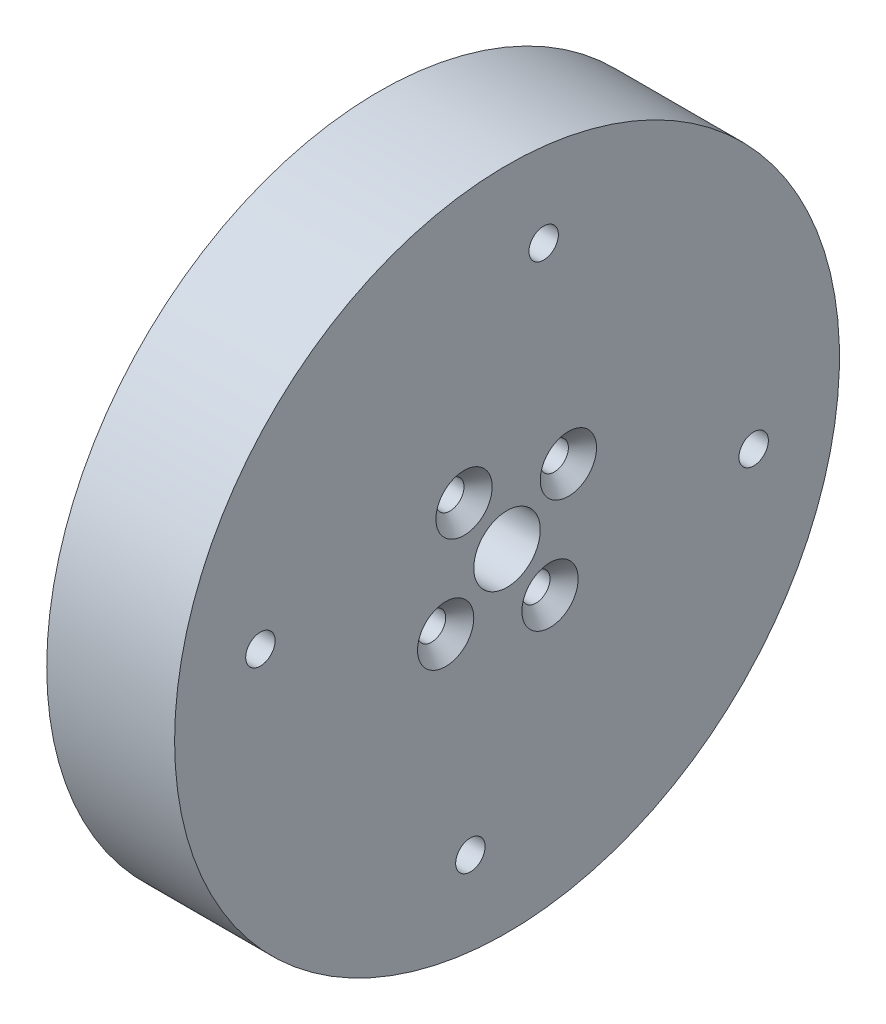
SolidWorks part; units mm, degrees
ref_plane "Спереди" through (0, 0, 0) normal (0, 0, 1) x (1, 0, 0)
ref_plane "Сверху" through (0, 0, 0) normal (0, 1, 0) x (1, 0, 0)
ref_plane "Справа" through (0, 0, 0) normal (1, 0, 0) x (0, 0, -1)
sketch "Эскиз1" plane through (0, 0, 0) normal (0, 0, 1) x (1, 0, 0)
  line L0 (0, 0) -> (100.9242, 0) construction
  line L6 (0, 13) -> (0, 26)
  line L7 (0, 26) -> (10, 26)
  line L11 (5, 13) -> (0, 13)
  line L13 (5, 13) -> (5, 2.6)
  line L14 (5, 2.6) -> (10, 2.6)
  line L15 (10, 2.6) -> (10, 26)
  dimension "D1" = 26
  dimension "D2" = 52
  dimension "D3" = 10
  dimension "D4" = 5
  dimension "D5" = 5.2
revolve "Повернуть1" add sketch "Эскиз1" angle 360 about L0
hole_wizard "Зенковка для  винта с плоской головкой M22" positions "Эскиз4" profile "Эскиз5" countersink size "M2" standard "Ansi Metric" end condition through all
sketch "Эскиз4" plane through (10, 0, 0) normal (1, 0, 0) x (0, 0, -1)
  point P0 (-3.3627, 4.8)
  dimension "D1" = 4.8
sketch "Эскиз5" plane through (10, 4.8, 3.3627) normal (0, 1, 0) x (0, 0, -1)
  line L0 (0, 0) -> (0, 10)
  line L1 (0, 10) -> (1.1, 10)
  line L2 (1.1, 10) -> (1.1, 1.1)
  line L3 (1.1, 1.1) -> (2.2, 0)
  line L5 (2.2, 0) -> (0, 0)
  line L6 (-1.1, 1.1) -> (-2.2, 0) construction
  line L11 (0, -6.35) -> (0, 107.95) construction
  dimension "Диаметр сквозного отверстия" = 2.2
  dimension "Глубина сквозного отверстия" = 10
  dimension "Диаметр передней зенковки" = 4.4
  dimension "Угол передней зенковки" = 90
ref_axis "Ось1" through (10, 0, 0) along (-1, 0, 0)
ref_axis "Ось2" through (10, 0, 0) along (-1, 0, 0)
pattern_circular "Круговой массив2" count 4 over 360 about axis through (10, 0, 0) along (-1, 0, 0) of "Зенковка для  винта с плоской головкой M22"
hole_wizard "Сверло под метчик  спиральное M2.21" positions "Эскиз6" profile "Эскиз7" hole size "M2.2x0.45" standard "Ansi Metric"
sketch "Эскиз6" plane through (10, 0, 0) normal (1, 0, 0) x (0, 0, -1)
  point P0 (19.2882, -2.8664)
  dimension "D1" = 19.5
sketch "Эскиз7" plane through (10, -2.8664, -19.2882) normal (0, 1, 0) x (0, 0, -1)
  line L0 (0, 0) -> (0, 3.691)
  line L1 (0, 3.691) -> (1.15, 3)
  line L2 (1.15, 3) -> (1.15, 0)
  line L5 (1.15, 0) -> (0, 0)
  line L10 (0, 3.691) -> (-1.15, 3) construction
  line L11 (0, -6.35) -> (0, 107.95) construction
  dimension "Диаметр отверстия" = 2.3
  dimension "Глубина отверстия" = 3
  dimension "Угол заточки сверла" = 118
pattern_circular "Круговой массив3" count 4 over 360 about axis through (10, 0, 0) along (-1, 0, 0) of "Сверло под метчик  спиральное M2.21"
